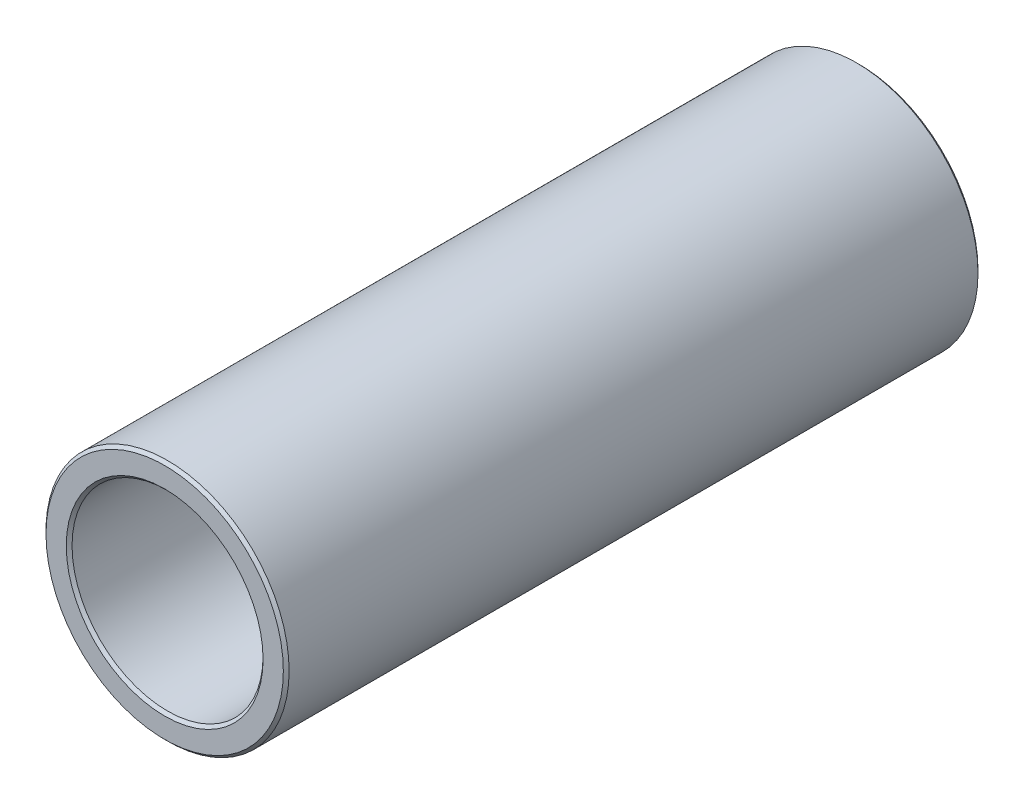
SolidWorks part; units mm, degrees
ref_plane "Płaszczyzna przednia" through (0, 0, 0) normal (0, 0, 1) x (1, 0, 0)
ref_plane "Płaszczyzna górna" through (0, 0, 0) normal (0, 1, 0) x (1, 0, 0)
ref_plane "Płaszczyzna prawa" through (0, 0, 0) normal (1, 0, 0) x (0, 0, -1)
sketch "Szkic1" plane through (0, 0, 0) normal (1, 0, 0) x (0, 0, -1)
  line L0 (-120, 0) -> (-120, 21)
  line L1 (-120, 21) -> (0, 21)
  line L2 (0, 21) -> (0, 0)
  line L3 (0, 0) -> (-120, 0)
  line L4 (0, 0) -> (-120, 0) construction
sketch "Szkic2" plane through (0, 0, 0) normal (1, 0, 0) x (0, 0, -1)
  line L0 (-120, 20.5) -> (-119.5, 21)
  line L1 (-119.5, 21) -> (-120, 21)
  line L2 (-120, 21) -> (-120, 20.5)
  line L3 (0, 0) -> (-120, 0) construction
sketch "Szkic3" plane through (0, 0, 0) normal (1, 0, 0) x (0, 0, -1)
  line L0 (-0.5, 21) -> (0, 20.5)
  line L1 (0, 20.5) -> (0, 21)
  line L2 (0, 21) -> (-0.5, 21)
  line L3 (0, 0) -> (-120, 0) construction
sketch "Szkic4" plane through (0, 0, 0) normal (1, 0, 0) x (0, 0, -1)
  line L0 (-13, 0) -> (-13, 16.5)
  line L1 (-13, 16.5) -> (-11.9175, 6.9175)
  line L2 (-11.9175, 6.9175) -> (-1.0825, 6.9175)
  line L3 (-1.0825, 6.9175) -> (0, 8)
  line L4 (0, 8) -> (0, 0)
  line L5 (0, 0) -> (-13, 0)
  line L6 (0, 0) -> (-13, 0) construction
sketch "Szkic5" plane through (0, 0, 0) normal (1, 0, 0) x (0, 0, -1)
  line L0 (-120, 0) -> (-120, 17)
  line L1 (-120, 17) -> (-119.5, 16.5)
  line L2 (-119.5, 16.5) -> (-13, 16.5)
  line L3 (-13, 16.5) -> (-13, 0)
  line L4 (-13, 0) -> (-120, 0)
  line L5 (-13, 0) -> (-120, 0) construction
revolve "Obrót1" add sketch "Szkic1" angle 360 about L4 reverse direction yes
revolve "Wycięcie-obrót1" cut sketch "Szkic2" angle 360 about L3 reverse direction yes
revolve "Wycięcie-obrót2" cut sketch "Szkic3" angle 360 about L3 reverse direction yes
revolve "Wycięcie-obrót3" cut sketch "Szkic4" angle 360 about L6 reverse direction yes
cosmetic thread "Oznaczenie gwintu1" parameters "D1"=12.0398, "D2"=16
cosmetic thread "Oznaczenie gwintu2" parameters "D2"=16
revolve "Wycięcie-obrót4" cut sketch "Szkic5" angle 360 about L5 reverse direction yes
ref_plane "Płaszczyzna1" through (0, 0, 120) normal (0, 0, 1) x (1, 0, 0)
ref_plane "IP2 XY" through (0, 0, 120) normal (0, 0, 1) x (1, 0, 0)
ref_plane "IP2 XZ" through (0, 0, 0) normal (0, -1, 0) x (-1, 0, 0)
ref_plane "IP2 YZ" through (0, 0, 0) normal (1, 0, 0) x (0, 0, -1)
ref_axis "IP2 X" through (-80.9, 0, 120) along (1, 0, 0)
ref_axis "IP2 Y" through (0, -50, 120) along (0, 1, 0)
ref_axis "IP2 Z" through (0, 0, 80.9) along (0, 0, -1)
sketch3d "IP2"
  point P0 (0, 0, 120)
ref_plane "IP1 XY" through (0, 0, 0) normal (0, 0, 1) x (1, 0, 0)
ref_plane "IP1 XZ" through (0, 0, 0) normal (0, -1, 0) x (-1, 0, 0)
ref_plane "IP1 YZ" through (0, 0, 0) normal (1, 0, 0) x (0, 0, -1)
ref_axis "IP1 X" through (-80.9, 0, 0) along (1, 0, 0)
ref_axis "IP1 Y" through (0, -50, 0) along (0, 1, 0)
ref_axis "IP1 Z" through (0, 0, 80.9) along (0, 0, -1)
sketch3d "IP1"
  point P0 (0, 0, 0)
